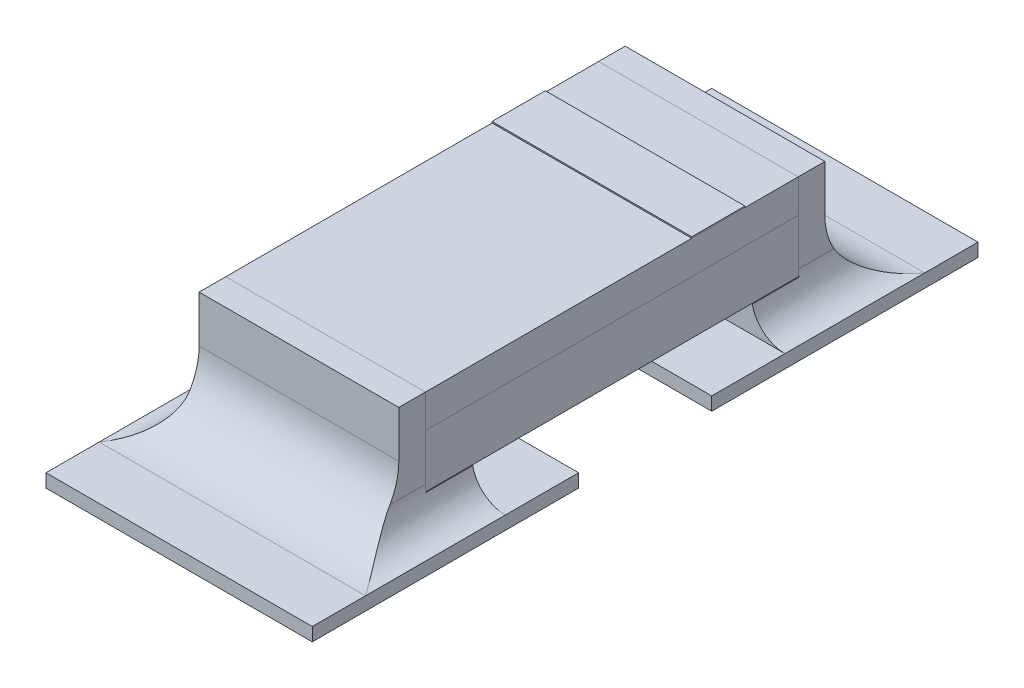
SolidWorks part; units mm, degrees
material "6063-O"
ref_plane "Front Plane" through (0, 0, 0) normal (0, 0, 1) x (1, 0, 0)
ref_plane "Top Plane" through (0, 0, 0) normal (0, 1, 0) x (1, 0, 0)
ref_plane "Right Plane" through (0, 0, 0) normal (1, 0, 0) x (0, 0, -1)
sketch "Sketch1" plane through (0, 0, 0) normal (0, 0, 1) x (1, 0, 0)
  line L0 (0, -55) -> (0, 55) construction
  line L1 (-0.75, 0.7) -> (0.75, 0.7)
  line L2 (-0.75, 0.7) -> (-0.75, 0.3)
  line L3 (-0.75, 0.3) -> (0.75, 0.3)
  line L4 (0.75, 0.7) -> (0.75, 0.3)
  line L5 (55, 0) -> (-55, 0) construction
  dimension "D1" = 1.5
  dimension "D2" = 0.75
  dimension "D3" = 0.3
  dimension "D4" = 0.4
extrude "Boss-Extrude1" add sketch "Sketch1" along normal mid plane 2.8
sketch "Sketch3" plane through (0, 0, 0) normal (1, 0, 0) x (0, 0, -1)
  line L0 (-1.4, 0.95) -> (-1.6, 0.95)
  line L1 (-1.6, 0.95) -> (-1.6, 0.1)
  line L2 (-1.6, 0.1) -> (-1.05, 0.1)
  line L3 (-1.05, 0.1) -> (-1.05, 0.3)
  line L4 (-1.4, 0.3) -> (1.4, 0.3) construction
  line L5 (-1.05, 0.3) -> (-1.4, 0.3)
  line L6 (-1.4, 0.3) -> (-1.4, 0.95)
  line L7 (1.4, 0.95) -> (1.6, 0.95)
  line L8 (1.6, 0.95) -> (1.6, 0.1)
  line L9 (1.6, 0.1) -> (1.05, 0.1)
  line L10 (1.05, 0.1) -> (1.05, 0.3)
  line L11 (1.05, 0.3) -> (1.4, 0.3)
  line L12 (1.4, 0.3) -> (1.4, 0.95)
  line L13 (55, 0) -> (-55, 0) construction
  dimension "D1" = 0.2
  dimension "D2" = 0.55
  dimension "D3" = 0.95
extrude "Boss-Extrude2" add sketch "Sketch3" along normal mid plane 1.5 separate body
sketch "Sketch5" plane through (0, 0, 0) normal (0, 0, 1) x (1, 0, 0)
  line L0 (-0.75, 0.95) -> (-0.75, 0.1) construction
  line L1 (0.75, 0.7) -> (-0.75, 0.7)
  line L2 (0.75, 0.7) -> (0.75, 0.95)
  line L3 (0.75, 0.95) -> (-0.75, 0.95)
  line L4 (-0.75, 0.7) -> (-0.75, 0.95)
  dimension "D1" = 0.25
extrude "Boss-Extrude4" add sketch "Sketch5" along normal mid plane 2.8 separate body
sketch "Sketch4" plane through (0, 0, 0) normal (0, 1, 0) x (1, 0, 0)
  line L1 (-1, 2.5) -> (1, 2.5)
  line L2 (-1, 2.5) -> (-1, 0.5)
  line L3 (-1, 0.5) -> (1, 0.5)
  line L4 (1, 2.5) -> (1, 0.5)
  line L5 (-1, -0.5) -> (1, -0.5)
  line L6 (-1, -0.5) -> (-1, -2.5)
  line L7 (-1, -2.5) -> (1, -2.5)
  line L8 (1, -0.5) -> (1, -2.5)
  line L10 (0, 0.5) -> (0, -0.5) construction
  dimension "D1" = 2
  dimension "D3" = 3
  dimension "D6" = 2
extrude "Boss-Extrude3" add sketch "Sketch4" along normal blind 0.1
sketch "Sketch6" plane through (0, 0.95, 0) normal (0, 1, 0) x (1, 0, 0)
  line L0 (-0.75, -1.4) -> (-0.75, 1.4) construction
  line L1 (-0.75, 1) -> (0.75, 1)
  line L2 (-0.75, 1) -> (-0.75, 0.6)
  line L3 (-0.75, 0.6) -> (0.75, 0.6)
  line L4 (0.75, 1) -> (0.75, 0.6)
  line L5 (0.75, -1.4) -> (0.75, 1.4) construction
  line L6 (-0.528, 0) -> (0.528, 0) construction
  dimension "D1" = 0.4
  dimension "D2" = 1
extrude "Boss-Extrude5" add sketch "Sketch6" along normal blind 0.01 separate body
fillet "Fillet1" radius 0.5 1 edges at (0, 0.1, 1.6)
fillet "Fillet2" radius 0.5 1 edges at (0, 0.1, -1.6)
fillet "Fillet3" radius 0.25 2 edges at (0.75, 0.1, -1.575) (-0.75, 0.1, -1.575)
fillet "Fillet4" radius 0.25 2 edges at (-0.75, 0.1, 1.575) (0.75, 0.1, 1.575)
